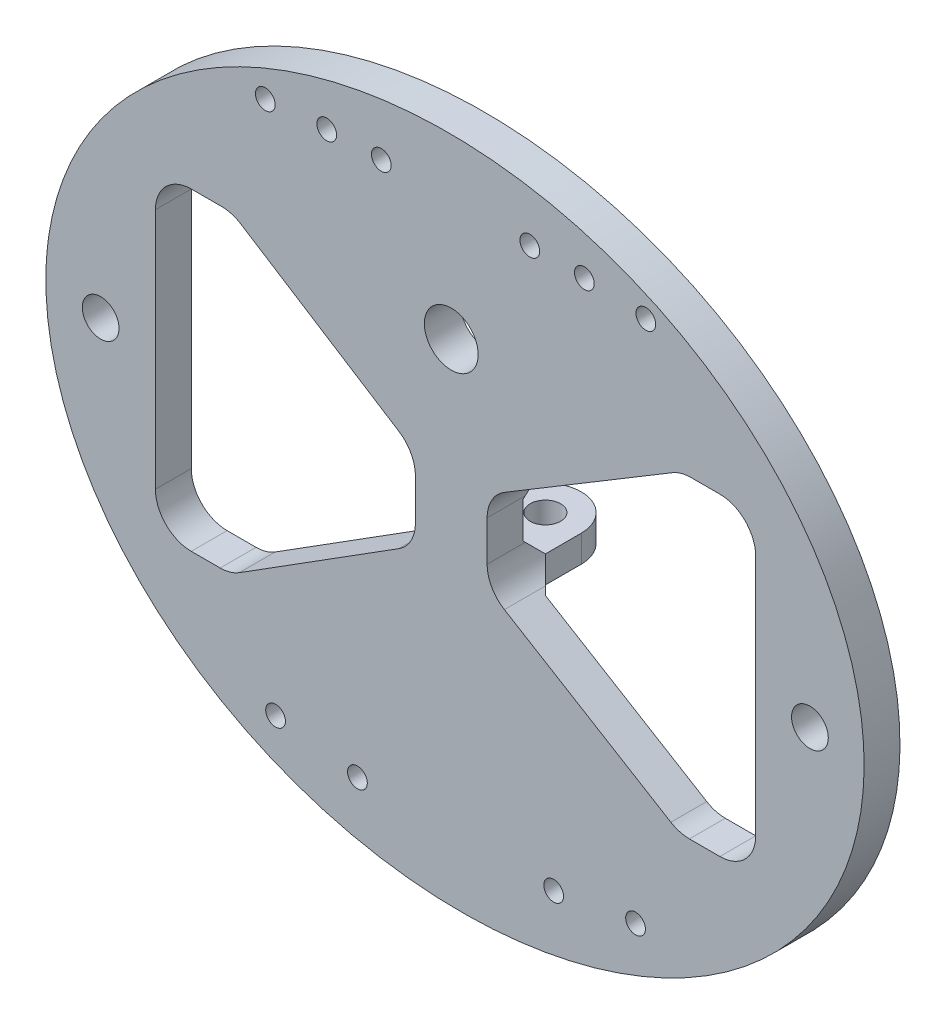
SolidWorks part; units mm, degrees
ref_plane "Front Plane" through (0, 0, 0) normal (0, 0, 1) x (1, 0, 0)
ref_plane "Top Plane" through (0, 0, 0) normal (0, 1, 0) x (1, 0, 0)
ref_plane "Right Plane" through (0, 0, 0) normal (1, 0, 0) x (0, 0, -1)
sketch "Sketch4" plane through (0, 0, 0) normal (0, 0, 1) x (1, 0, 0)
  line L0 (-9.465, 23.2997) -> (40.6023, 23.2997)
  line L1 (40.6023, 23.2997) -> (40.6023, 15.2997)
  line L2 (40.6023, 15.2997) -> (48.9468, 15.2997)
  line L3 (48.9468, 15.2997) -> (48.9468, -19.7003)
  line L4 (48.9468, -19.7003) -> (40.4354, -19.7003)
  line L5 (40.4354, -19.7003) -> (40.4354, -27.7003)
  line L6 (40.4354, -27.7003) -> (-9.6319, -27.7003)
  line L7 (-9.6319, -27.7003) -> (-9.6319, -19.7003)
  line L8 (-9.6319, -19.7003) -> (-18.014, -19.7003)
  line L9 (-18.014, -19.7003) -> (-18.014, 15.2997)
  line L10 (-18.014, 15.2997) -> (-9.465, 15.2997)
  line L11 (-9.465, 23.2997) -> (-9.465, 15.2997)
  ellipse E0 centre (15.4017, -2.1989) end of major axis (-30.2131, -0.4261) minor radius 37.27
extrude "Boss-Extrude2" add sketch "Sketch4" along normal blind 4
sketch "Sketch9" plane through (0, 0, 0) normal (0, 0, -1) x (-1, 0, 0)
  line L0 (-48.9468, -2.2003) -> (18.014, -2.2003) construction
  line L1 (-48.9468, -19.7003) -> (-48.9468, 15.2997) construction
  line L2 (18.014, 15.2997) -> (18.014, -19.7003) construction
  line L3 (-40.6023, 23.2997) -> (-40.6023, 15.2997)
  line L4 (-18.986, 2.2997) -> (-10.986, 2.2997) construction
  line L5 (-18.986, 2.2997) -> (-18.986, -6.7003) construction
  line L6 (-18.986, -6.7003) -> (-10.986, -6.7003) construction
  line L7 (-10.986, 2.2997) -> (-10.986, -6.7003) construction
  line L8 (-18.986, 2.2997) -> (-10.986, -6.7003) construction
  line L9 (-18.986, -6.7003) -> (-10.986, 2.2997) construction
  line L10 (-18.986, 2.2997) -> (-10.986, 2.2997)
  line L11 (-18.986, 2.2997) -> (-18.986, 5.2997)
  line L12 (-18.986, 5.2997) -> (-10.986, 5.2997)
  line L13 (-10.986, 2.2997) -> (-10.986, 5.2997)
  line L14 (-10.986, -6.7003) -> (-18.986, -6.7003)
  line L15 (-10.986, -6.7003) -> (-10.986, -9.7003)
  line L16 (-10.986, -9.7003) -> (-18.986, -9.7003)
  line L17 (-18.986, -6.7003) -> (-18.986, -9.7003)
  point P6 (-14.986, -2.2003)
  dimension "D1" = 8
  dimension "D2" = 9
  dimension "D3" = 33
  dimension "D4" = 3
  dimension "D5" = 3
extrude "Boss-Extrude5" add sketch "Sketch9" along normal blind 10.5 separate body contours L10 L13 L12 L11 | L14 L17 L16 L15 region at (14.986, 3.7997, 0) region at (14.986, -8.2003, 0)
fillet "Fillet2" radius 4 2 edges at (18.986, -8.2003, -10.5) (10.986, -8.2003, -10.5)
fillet "Fillet3" radius 4 2 edges at (18.986, 3.7997, -10.5) (10.986, 3.7997, -10.5)
sketch "Sketch10" plane through (0, 5.2997, 0) normal (0, 1, 0) x (1, 0, 0)
  circle A0 centre (14.986, 6.5) radius 1.7
  dimension "D1" = 3.4
extrude "Cut-Extrude1" cut sketch "Sketch10" against normal through all
sketch "Sketch11" plane through (0, 0, 4) normal (0, 0, 1) x (1, 0, 0)
  line L0 (-9.465, 15.2997) -> (10.986, 2.2997)
  line L1 (10.986, 2.2997) -> (18.986, 2.2997)
  line L2 (18.986, 2.2997) -> (40.6023, 15.2997)
  line L3 (40.6023, 15.2997) -> (40.6023, 23.2997)
  line L10 (-9.465, 23.2997) -> (-9.465, 15.2997)
  line L11 (10.986, -6.7003) -> (18.986, -6.7003)
  line L12 (18.986, -6.7003) -> (40.4354, -19.7003)
  line L13 (40.4354, -19.7003) -> (40.4354, -27.7003)
  line L20 (-9.6319, -27.7003) -> (-9.6319, -19.7003)
  line L21 (-9.6319, -19.7003) -> (10.986, -6.7003)
  line L23 (40.6023, 23.2997) -> (-9.465, 23.2997) construction
  line L24 (15.5686, 23.2997) -> (-9.465, 23.2997)
  line L26 (40.6023, 23.2997) -> (15.5686, 23.2997)
  line L27 (-9.6319, -27.7003) -> (40.4354, -27.7003)
extrude "Boss-Extrude8" add sketch "Sketch11" against normal up to surface (4 mm away) up to face at (14.986, 3.7997, 0)
sketch "Sketch12" plane through (0, 0, 4) normal (0, 0, 1) x (1, 0, 0)
  circle A0 centre (14.986, 15.2997) radius 3
extrude "Cut-Extrude2" cut sketch "Sketch12" against normal blind 16
sketch "Sketch16" plane through (0, 0, 4) normal (0, 0, 1) x (1, 0, 0)
  line L0 (-18.014, -2.2003) -> (48.9468, -2.2003) construction
  line L1 (-18.014, 15.2997) -> (-18.014, -19.7003) construction
  line L2 (48.9468, -19.7003) -> (48.9468, 15.2997) construction
  line L3 (48.9468, 15.2997) -> (-18.014, -19.7003) construction
  line L4 (-18.014, 15.2997) -> (48.9468, -19.7003) construction
  line L5 (15.4664, -2.2003) -> (-5.7559, 28.1083) construction
  line L6 (15.4664, -2.2003) -> (1.0974, 28.6141) construction
  line L7 (15.4664, -2.2003) -> (7.1842, 28.7093) construction
  line L8 (15.4664, -2.2003) -> (15.4664, 31.0561) construction
  line L9 (15.4664, -2.2003) -> (23.7486, 28.7093) construction
  line L10 (15.4664, -2.2003) -> (29.8354, 28.6141) construction
  line L11 (15.4664, -2.2003) -> (36.6887, 28.1083) construction
  line L12 (15.4664, -2.2003) -> (-4.6088, -30.8706) construction
  line L13 (15.4664, -2.2003) -> (4.5217, -32.2705) construction
  line L14 (15.4664, -2.2003) -> (15.4664, -36.5096) construction
  line L15 (15.4664, -2.2003) -> (26.411, -32.2705) construction
  line L16 (15.4664, -2.2003) -> (35.5416, -30.8706) construction
  circle A0 centre (-5.7559, 28.1083) radius 1.1
  circle A1 centre (1.0974, 28.6141) radius 1.1
  circle A2 centre (7.1842, 28.7093) radius 1.1
  circle A3 centre (23.7486, 28.7093) radius 1.1
  circle A4 centre (29.8354, 28.6141) radius 1.1
  circle A5 centre (36.6887, 28.1083) radius 1.1
  circle A6 centre (-4.6088, -30.8706) radius 1.1
  circle A7 centre (4.5217, -32.2705) radius 1.1
  circle A8 centre (26.411, -32.2705) radius 1.1
  circle A9 centre (35.5416, -30.8706) radius 1.1
  dimension "D1" = 15
  dimension "D2" = 10
  dimension "D3" = 10
  dimension "D4" = 15
  dimension "D5" = 10
  dimension "D6" = 10
  dimension "D7" = 15
  dimension "D8" = 20
  dimension "D9" = 20
  dimension "D10" = 15
  dimension "D11" = 35
  dimension "D12" = 32
  dimension "D13" = 32
  dimension "D14" = 35
  dimension "D15" = 37
  dimension "D16" = 34
  dimension "D17" = 32
  dimension "D18" = 32
  dimension "D19" = 34
  dimension "D20" = 37
extrude "Cut-Extrude3" cut sketch "Sketch16" against normal blind 16
sketch "Sketch17" plane through (0, 0, 4) normal (0, 0, 1) x (1, 0, 0)
  line L1 (18.986, -6.7003) -> (10.986, -6.7003)
  line L2 (18.986, -6.7003) -> (18.986, 2.2997)
  line L3 (18.986, 2.2997) -> (10.986, 2.2997)
  line L4 (10.986, -6.7003) -> (10.986, 2.2997)
extrude "Boss-Extrude9" add sketch "Sketch17" against normal up to surface (4 mm away) up to face at (37.7887, 28.1083, 0)
fillet "Fillet4" radius 4 12 edges at (-9.465, 15.2997, 2) (-18.014, 15.2997, 2) (-18.014, -19.7003, 2) (-9.6319, -19.7003, 2) (40.4354, -19.7003, 2) (40.6023, 15.2997, 2) (48.9468, 15.2997, 2) (48.9468, -19.7003, 2) (10.986, -6.7003, 2) (10.986, 2.2997, 2) (18.986, -6.7003, 2) (18.986, 2.2997, 2)
chamfer "Chamfer6" distance 2.5 angle 45 8 edges at (10.986, -8.2003, 0) (14.986, -9.7003, 0) (18.986, -8.2003, 0) (14.986, -6.7003, 0) (14.986, 2.2997, 0) (10.986, 3.7997, 0) (14.986, 5.2997, 0) (18.986, 3.7997, 0)
sketch "Sketch18" plane through (0, 0, 4) normal (0, 0, 1) x (1, 0, 0)
  line L0 (-18.014, -2.2003) -> (-30.2303, -2.2003) construction
  line L1 (-18.014, 11.2997) -> (-18.014, -15.7003) construction
  line L2 (48.9468, -2.2003) -> (61.0338, -2.2003) construction
  line L3 (48.9468, -15.7003) -> (48.9468, 11.2997) construction
  circle A0 centre (-24.1222, -2.2003) radius 2.05
  circle A1 centre (54.9903, -2.2003) radius 2.05
  ellipse E0 centre (15.4017, -2.1989) end of major axis (-30.2131, -0.4261) minor radius 37.27 construction
  dimension "D1" = 4.1
  dimension "D2" = 4.1
extrude "Cut-Extrude4" cut sketch "Sketch18" against normal blind 10
